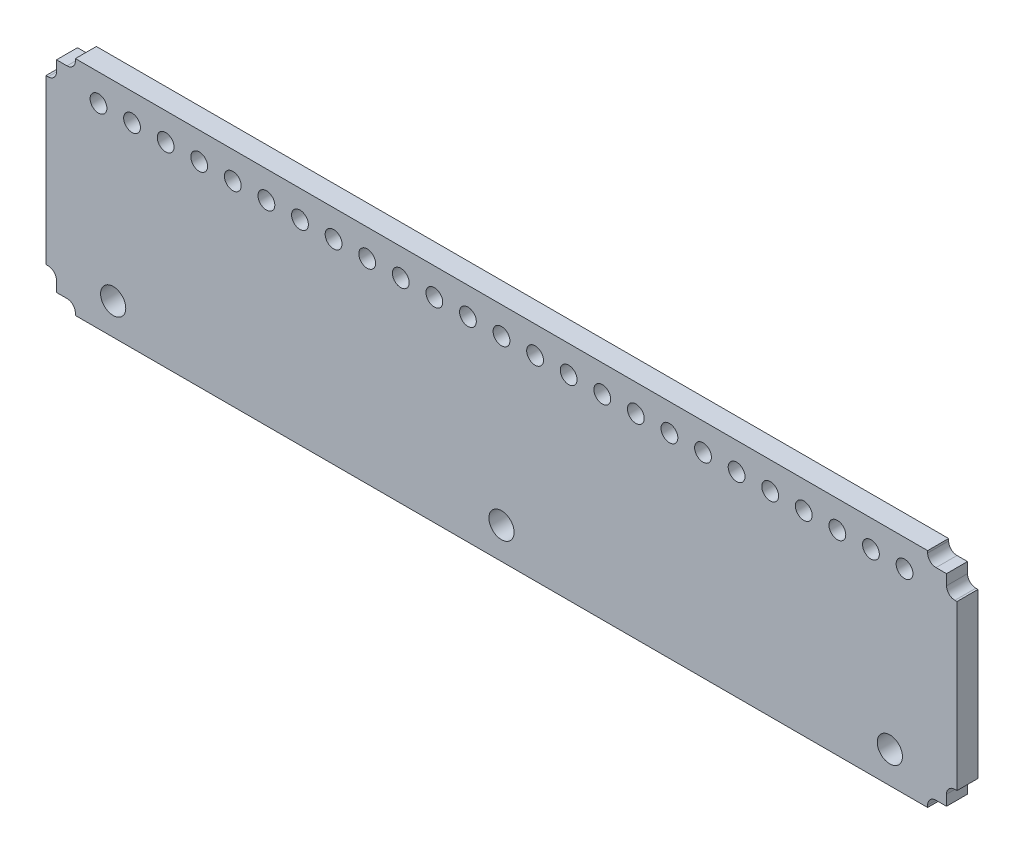
SolidWorks part; units mm, degrees
ref_plane "Front Plane" through (0, 0, 0) normal (0, 0, 1) x (1, 0, 0)
ref_plane "Top Plane" through (0, 0, 0) normal (0, 1, 0) x (1, 0, 0)
ref_plane "Right Plane" through (0, 0, 0) normal (1, 0, 0) x (0, 0, -1)
sketch "Sketch1" plane through (0, 0, 0) normal (0, 0, 1) x (1, 0, 0)
  line L1 (336.55, 76.2) -> (-336.55, 76.2)
  line L2 (336.55, 76.2) -> (336.55, -76.2)
  line L3 (336.55, -76.2) -> (-336.55, -76.2)
  line L4 (-336.55, 76.2) -> (-336.55, -76.2)
  line L5 (336.55, 76.2) -> (-336.55, -76.2) construction
  line L6 (336.55, -76.2) -> (-336.55, 76.2) construction
  point P0 (0, 0)
  dimension "D1" = 673.1
  dimension "D2" = 152.4
extrude "Boss-Extrude1" add sketch "Sketch1" along normal mid plane 15.875
sketch "Sketch2" plane through (0, 0, 7.9375) normal (0, 0, 1) x (1, 0, 0)
  line L0 (-336.55, 76.2) -> (-336.55, -76.2) construction
  line L1 (-336.55, 61.9125) -> (-344.4875, 61.9125)
  line L2 (-336.55, 61.9125) -> (-336.55, -61.9125)
  line L3 (-336.55, -61.9125) -> (-344.4875, -61.9125)
  line L4 (-344.4875, 61.9125) -> (-344.4875, -61.9125)
  line L5 (336.55, 76.2) -> (-336.55, 76.2) construction
  line L6 (-322.2625, 76.2) -> (322.2625, 76.2)
  line L7 (-322.2625, 76.2) -> (-322.2625, 84.1375)
  line L8 (-322.2625, 84.1375) -> (322.2625, 84.1375)
  line L9 (322.2625, 76.2) -> (322.2625, 84.1375)
  line L10 (-336.55, -76.2) -> (336.55, -76.2) construction
  line L11 (-322.2625, -76.2) -> (322.2625, -76.2)
  line L12 (-322.2625, -76.2) -> (-322.2625, -84.1375)
  line L13 (-322.2625, -84.1375) -> (322.2625, -84.1375)
  line L14 (322.2625, -76.2) -> (322.2625, -84.1375)
  line L15 (336.55, -76.2) -> (336.55, 76.2) construction
  line L16 (336.55, 61.9125) -> (344.4875, 61.9125)
  line L17 (336.55, 61.9125) -> (336.55, -61.9125)
  line L18 (336.55, -61.9125) -> (344.4875, -61.9125)
  line L19 (344.4875, 61.9125) -> (344.4875, -61.9125)
  line L20 (0, 0) -> (0, 76.2) construction
  line L21 (0, 0) -> (-336.55, 0) construction
  dimension "D1" = 14.2875
  dimension "D2" = 14.2875
  dimension "D3" = 7.9375
  dimension "D4" = 168.275
  dimension "D5" = 688.975
extrude "Boss-Extrude2" add sketch "Sketch2" against normal up to surface (15.875 mm away) up to face at (0, 0, -7.9375)
fillet "Fillet1" radius 6.35 8 edges at (336.55, 61.9125, 0) (336.55, -61.9125, 0) (322.2625, -76.2, 0) (-322.2625, -76.2, 0) (-322.2625, 76.2, 0) (-336.55, -61.9125, 0) (-336.55, 61.9125, 0) (322.2625, 76.2, 0)
sketch "Sketch3" plane through (0, 0, 7.9375) normal (0, 0, 1) x (1, 0, 0)
  line L0 (344.4875, -61.9125) -> (344.4875, 61.9125) construction
  line L1 (0, 0) -> (0, -34.2486) construction
  line L2 (336.55, 76.2) -> (328.6125, 76.2) construction
  circle A0 centre (0, -60.325) radius 9.525
  circle A2 centre (0, 63.5) radius 6.35
  circle A3 centre (25.4, 63.5) radius 6.35
  circle A4 centre (50.8, 63.5) radius 6.35
  circle A5 centre (76.2, 63.5) radius 6.35
  circle A6 centre (101.6, 63.5) radius 6.35
  circle A7 centre (127, 63.5) radius 6.35
  circle A8 centre (152.4, 63.5) radius 6.35
  circle A9 centre (177.8, 63.5) radius 6.35
  circle A10 centre (203.2, 63.5) radius 6.35
  circle A11 centre (228.6, 63.5) radius 6.35
  circle A12 centre (254, 63.5) radius 6.35
  circle A13 centre (279.4, 63.5) radius 6.35
  circle A14 centre (304.8, 63.5) radius 6.35
  circle A15 centre (-25.4, 63.5) radius 6.35
  circle A16 centre (-50.8, 63.5) radius 6.35
  circle A17 centre (-76.2, 63.5) radius 6.35
  circle A18 centre (-101.6, 63.5) radius 6.35
  circle A19 centre (-127, 63.5) radius 6.35
  circle A20 centre (-152.4, 63.5) radius 6.35
  circle A21 centre (-177.8, 63.5) radius 6.35
  circle A22 centre (-203.2, 63.5) radius 6.35
  circle A23 centre (-228.6, 63.5) radius 6.35
  circle A24 centre (-254, 63.5) radius 6.35
  circle A25 centre (-279.4, 63.5) radius 6.35
  circle A26 centre (-304.8, 63.5) radius 6.35
  circle A27 centre (293.6875, -60.325) radius 9.525
  circle A28 centre (-293.6875, -60.325) radius 9.525
  dimension "D1" = 60.325
  dimension "D2" = 19.05
  dimension "D4" = 12.7
  dimension "D7" = 50.8
  dimension "D3" = 12.7
  dimension "D5" = 13
  dimension "D6" = 13
extrude "Cut-Extrude1" cut sketch "Sketch3" against normal through all both and the other way through all
